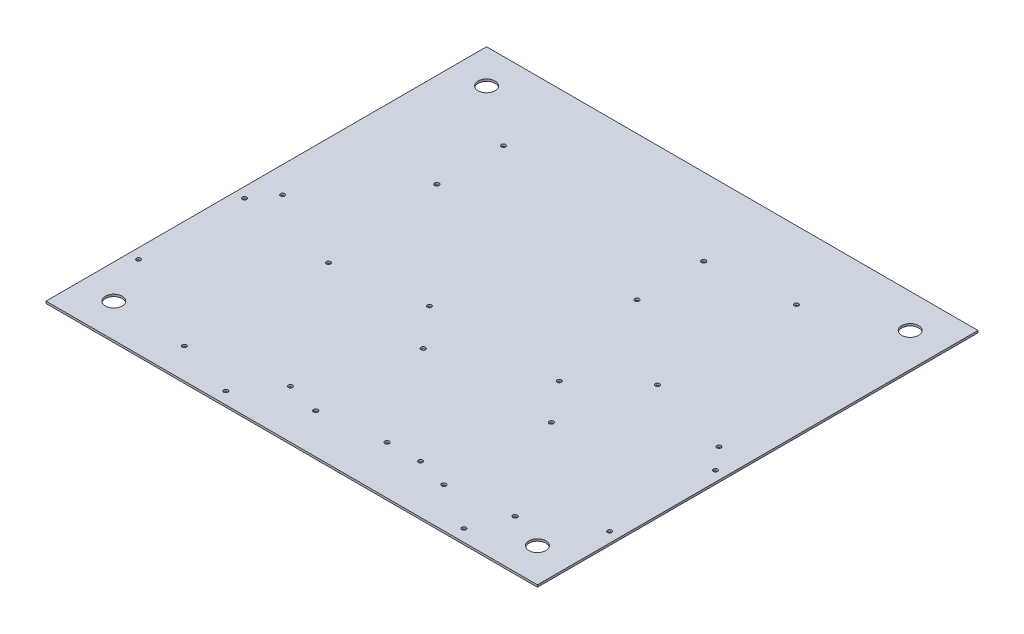
SolidWorks part; units mm, degrees
ref_plane "Front Plane" through (0, 0, 0) normal (0, 0, 1) x (1, 0, 0)
ref_plane "Top Plane" through (0, 0, 0) normal (0, 1, 0) x (1, 0, 0)
ref_plane "Right Plane" through (0, 0, 0) normal (1, 0, 0) x (0, 0, -1)
sketch "Sketch1" plane through (0, 0, 0) normal (0, 1, 0) x (1, 0, 0)
  line L1 (-184.15, 165.1) -> (184.15, 165.1)
  line L2 (-184.15, 165.1) -> (-184.15, -165.1)
  line L3 (-184.15, -165.1) -> (184.15, -165.1)
  line L4 (184.15, 165.1) -> (184.15, -165.1)
  line L5 (-184.15, 165.1) -> (184.15, -165.1) construction
  line L6 (-184.15, -165.1) -> (184.15, 165.1) construction
  point P0 (0, 0)
  dimension "D1" = 330.2
  dimension "D2" = 368.3
extrude "Boss-Extrude1" add sketch "Sketch1" along normal blind 1.5875
sketch "Sketch2" plane through (0, 1.5875, 0) normal (0, 1, 0) x (1, 0, 0)
  line L0 (0, 165.1) -> (0, -165.1) construction
  line L1 (-184.15, 165.1) -> (184.15, 165.1) construction
  line L2 (-184.15, 165.1) -> (-184.15, -165.1) construction
  line L3 (-184.15, -165.1) -> (184.15, -165.1) construction
  line L4 (184.15, 165.1) -> (184.15, -165.1) construction
  line L5 (-184.15, 165.1) -> (184.15, -165.1) construction
  line L6 (-184.15, -165.1) -> (184.15, 165.1) construction
  line L7 (-184.15, 0) -> (184.15, 0) construction
  circle A0 centre (-158.75, -139.7) radius 6.35
  circle A4 centre (158.75, -139.7) radius 6.35
  circle A5 centre (-158.75, 139.7) radius 6.35
  circle A6 centre (158.75, 139.7) radius 6.35
  point P0 (0, 0)
  dimension "D2" = 25.4
  dimension "D3" = 25.4
  dimension "D4" = 12.7
  dimension "D1" = 330.2
  dimension "D5" = 368.3
extrude "Cut-Extrude1" cut sketch "Sketch2" against normal up to next
sketch "Sketch3" plane through (0, 0, 0) normal (0, -1, 0) x (1, 0, 0)
  circle A0 centre (-11.9099, 135.1844) radius 1.665
  circle A1 centre (35.3434, 128.9763) radius 1.665
  circle A2 centre (-12.0376, 54.4642) radius 1.665
  circle A3 centre (84.1208, 135.1844) radius 1.665
  circle A4 centre (131.3741, 128.9763) radius 1.665
  circle A5 centre (83.9931, 54.4642) radius 1.665
  dimension "D1" = 3.33
extrude "Cut-Extrude2" cut sketch "Sketch3" against normal up to next
sketch "Sketch4" plane through (0, 1.5875, 0) normal (0, 1, 0) x (1, 0, 0)
  circle A0 centre (36.45, 107.2) radius 1.1727 construction
  circle A1 centre (36.45, 57.2) radius 1.1727 construction
  circle A2 centre (-113.55, 107.2) radius 1.1727 construction
  circle A3 centre (-113.55, 57.2) radius 1.1727 construction
  circle A4 centre (36.45, 107.2) radius 1.1727 construction
  circle A5 centre (36.45, 57.2) radius 1.1727 construction
  circle A6 centre (-113.55, 107.2) radius 1.1727 construction
  circle A7 centre (-113.55, 57.2) radius 1.1727 construction
  circle A8 centre (-113.55, 57.2) radius 1.665
  circle A9 centre (-113.55, 107.2) radius 1.665
  circle A10 centre (36.45, 107.2) radius 1.665
  circle A11 centre (36.45, 57.2) radius 1.665
  dimension "D1" = 3.33
extrude "Cut-Extrude3" cut sketch "Sketch4" against normal up to next
sketch "Sketch5" plane through (0, 1.5875, 0) normal (0, 1, 0) x (1, 0, 0)
  circle A0 centre (-103.15, -142.4) radius 1.5875
  circle A1 centre (-103.15, -34.4) radius 1.5875
  circle A2 centre (-176.53, -103.365) radius 1.5875
  circle A3 centre (-176.53, -23.99) radius 1.5875
  circle A4 centre (-164.465, -7.48) radius 1.5875
  circle A5 centre (162.56, -7.48) radius 1.5875
  circle A6 centre (99.3724, 9.665) radius 1.5875
  circle A7 centre (99.3724, 113.805) radius 1.5875
  circle A8 centre (176.53, -103.365) radius 1.5875
  circle A9 centre (176.53, -23.99) radius 1.5875
  circle A10 centre (120.02, -156.07) radius 1.5875
  circle A11 centre (-58.415, -156.07) radius 1.5875
  circle A12 centre (-37.2337, -128.765) radius 1.5875
  circle A13 centre (-37.2337, -24.625) radius 1.5875
  circle A14 centre (60.1245, -128.765) radius 1.5875
  circle A15 centre (60.1245, -24.625) radius 1.5875
  dimension "D1" = 3.175
extrude "Cut-Extrude4" cut sketch "Sketch5" against normal blind 2.54
